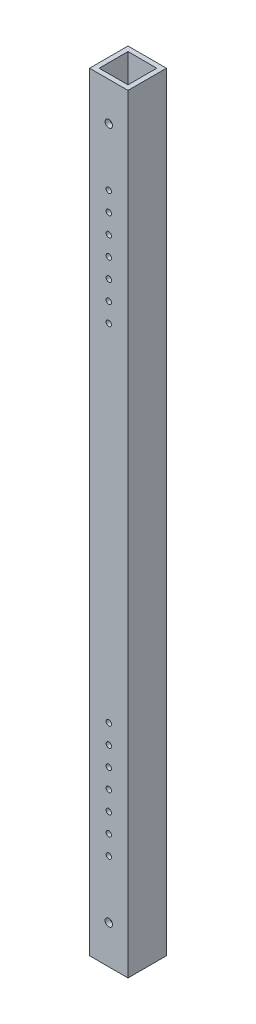
SolidWorks part; units mm, degrees
material "6061-T6 (SS)"
ref_plane "Front Plane" through (0, 0, 0) normal (0, 0, 1) x (1, 0, 0)
ref_plane "Top Plane" through (0, 0, 0) normal (0, 1, 0) x (1, 0, 0)
ref_plane "Right Plane" through (0, 0, 0) normal (1, 0, 0) x (0, 0, -1)
sketch "Sketch1" plane through (0, 0, 0) normal (0, 1, 0) x (1, 0, 0)
  line L0 (9.525, 9.525) -> (-9.525, 9.525)
  line L1 (12.7, -12.7) -> (-12.7, -12.7)
  line L2 (12.7, -12.7) -> (12.7, 12.7)
  line L3 (12.7, 12.7) -> (-12.7, 12.7)
  line L4 (-12.7, -12.7) -> (-12.7, 12.7)
  line L5 (12.7, -12.7) -> (-12.7, 12.7) construction
  line L6 (12.7, 12.7) -> (-12.7, -12.7) construction
  line L7 (-9.525, -9.525) -> (-9.525, 9.525)
  line L8 (9.525, -9.525) -> (-9.525, -9.525)
  line L9 (9.525, -9.525) -> (9.525, 9.525)
  point P0 (0, 0)
  dimension "D1" = 25.4
  dimension "D2" = 25.4
  dimension "D3" = 3.175
extrude "Boss-Extrude1" add sketch "Sketch1" along normal mid plane 508
sketch "Sketch2" plane through (0, 0, -12.7) normal (0, 0, -1) x (-1, 0, 0)
  line L0 (-12.7, 254) -> (12.7, 254) construction
  line L1 (12.7, 254) -> (12.7, -254) construction
  line L2 (-12.7, -254) -> (12.7, -254) construction
  point P0 (0, 228.6)
  point P1 (0, -228.6)
  point P3 (0, 254)
  point P8 (0, -254)
  dimension "D1" = 25.4
  dimension "D2" = 12.7
  dimension "D3" = 25.4
  dimension "D4" = 12.7
hole_wizard "#10 (0.1935) Diameter Hole1" positions "Sketch4" profile "Sketch3" hole size "#10" standard "ANSI Inch"
sketch "Sketch4" plane through (0, 0, -12.7) normal (0, 0, -1) x (-1, 0, 0)
  point P0 (0, 228.6)
  point P3 (0, -228.6)
sketch "Sketch3" plane through (0, 228.6, -12.7) normal (1, 0, 0) x (0, 1, 0)
  line L0 (0, 0) -> (0, 52.2766)
  line L1 (0, 52.2766) -> (2.4574, 50.8)
  line L2 (2.4574, 50.8) -> (2.4574, 0)
  line L5 (2.4574, 0) -> (0, 0)
  line L10 (0, 52.2766) -> (-2.4575, 50.8) construction
  line L11 (0, -6.35) -> (0, 107.95) construction
  dimension "Hole Dia." = 4.9149
  dimension "Hole Depth" = 50.8
  dimension "Drill Angle" = 118
sketch "Sketch5" plane through (0, 0, 12.7) normal (0, 0, 1) x (1, 0, 0)
  line L1 (-12.7, 254) -> (12.7, 254) construction
  circle A0 centre (0, 190.5) radius 1.778
  circle A1 centre (0, 139.7) radius 1.778
  circle A2 centre (0, 177.8) radius 1.778
  circle A3 centre (0, 165.1) radius 1.778
  circle A4 centre (0, 152.4) radius 1.778
  circle A5 centre (0, 127) radius 1.778
  circle A6 centre (0, 114.3) radius 1.778
  dimension "D1" = 63.5
  dimension "D3" = 7
extrude "Cut-Extrude1" cut sketch "Sketch5" against normal through all
mirror "Mirror1" about plane through (0, 0, 0) normal (0, 1, 0) of "Cut-Extrude1"
